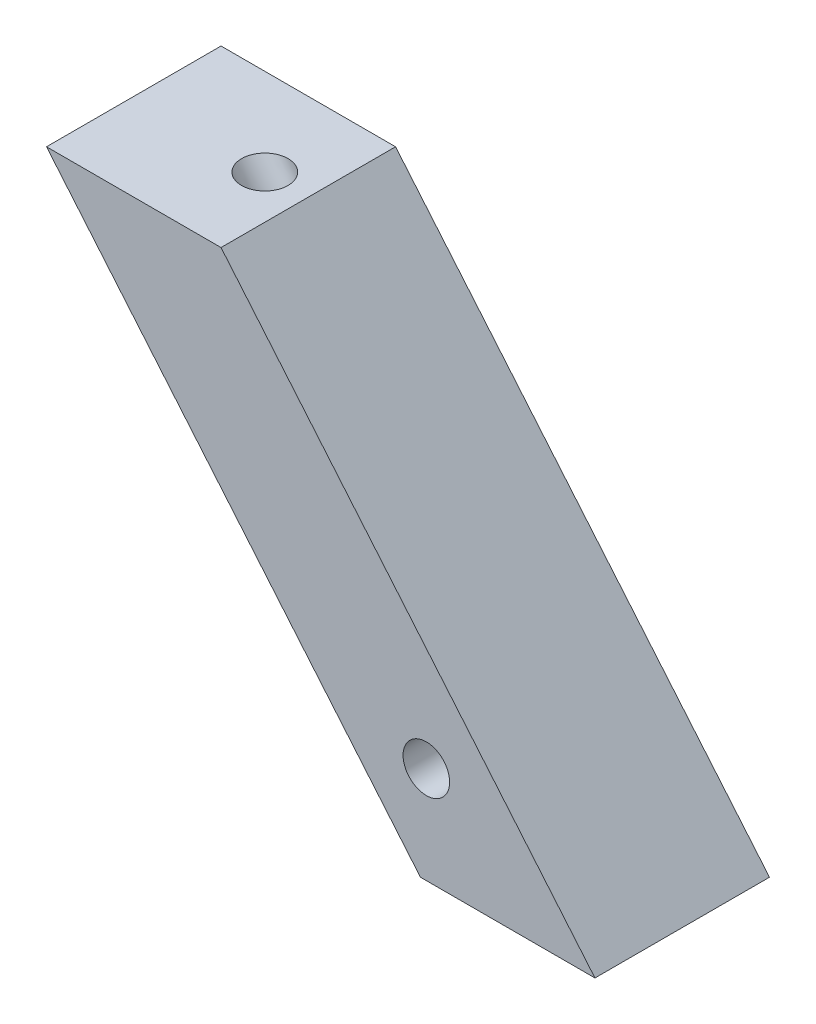
SolidWorks part; units mm, degrees
ref_plane "前视基准面" through (0, 0, 0) normal (0, 0, 1) x (1, 0, 0)
ref_plane "上视基准面" through (0, 0, 0) normal (0, 1, 0) x (1, 0, 0)
ref_plane "右视基准面" through (0, 0, 0) normal (1, 0, 0) x (0, 0, -1)
other "Configuration Table"
sketch "草图1" plane through (0, 0, 0) normal (0, 1, 0) x (1, 0, 0)
  line L1 (-73.0693, 17.1535) -> (16.9307, 17.1535)
  line L2 (-73.0693, 17.1535) -> (-73.0693, -72.8465)
  line L3 (-73.0693, -72.8465) -> (16.9307, -72.8465)
  line L4 (16.9307, 17.1535) -> (16.9307, -72.8465)
  dimension "D1" = 90
sketch "草图2" plane through (0, 0, 0) normal (0, 0, 1) x (1, 0, 0)
  line L0 (-28.0693, 0) -> (-220.9056, 229.8133)
  line L1 (-73.0693, 0) -> (16.9307, 0) construction
  dimension "D1" = 300
  dimension "D2" = 50
sweep "扫描1" add profiles "草图1" path "草图2"
sketch "草图3" plane through (0, 0, 0) normal (0, -1, 0) x (1, 0, 0)
  line L0 (-28.0693, 72.8465) -> (-28.0693, -17.1535) construction
  line L1 (-73.0693, 72.8465) -> (16.9307, 72.8465) construction
  line L2 (16.9307, -17.1535) -> (-73.0693, -17.1535) construction
  line L3 (-73.0693, 27.8465) -> (16.9307, 27.8465) construction
  line L4 (-73.0693, -17.1535) -> (-73.0693, 72.8465) construction
  line L5 (16.9307, 72.8465) -> (16.9307, -17.1535) construction
  point P12 (-5.0693, 50.8465)
  point P14 (-5.0693, 4.8465)
  point P15 (-51.0693, 4.8465)
  point P16 (-51.0693, 50.8465)
  dimension "D1" = 46
  dimension "D2" = 46
hole_wizard "M4 螺纹孔1" positions "3D草图1" profile "草图4" tap size "M4" standard "GB"
sketch3d "3D草图1"
  point P0 (-51.0693, 0, 50.8465)
  point P3 (-5.0693, 0, 50.8465)
  point P6 (-5.0693, 0, 4.8465)
  point P9 (-51.0693, 0, 4.8465)
sketch "草图4" plane through (-51.0693, 0, 50.8465) normal (1, 0, 0) x (0, 0, -1)
  line L0 (0, 0) -> (0, 16.9914)
  line L1 (0, 16.9914) -> (1.65, 16)
  line L2 (1.65, 16) -> (1.65, 0)
  line L5 (1.65, 0) -> (0, 0)
  line L10 (0, 16.9914) -> (-1.65, 16) construction
  line L11 (0, -6.35) -> (0, 107.95) construction
  dimension "螺纹孔钻头直径" = 3.3
  dimension "螺纹孔钻头深度" = 16
  dimension "导头角度" = 118
cosmetic thread "孔螺蚊线1" parameters "D1"=18, "D2"=4
cosmetic thread "孔螺蚊线2" parameters "D1"=18, "D2"=4
cosmetic thread "孔螺蚊线3" parameters "D1"=18, "D2"=4
cosmetic thread "孔螺蚊线4" parameters "D1"=18, "D2"=4
sketch "草图5" plane through (0, 0, 0) normal (0, -1, 0) x (1, 0, 0)
  line L0 (-28.0693, 72.8465) -> (-28.0693, -17.1535) construction
  circle A0 centre (-28.0693, 27.8465) radius 12
  dimension "D1" = 24
sketch "草图8" plane through (0, 0, 72.8465) normal (0, 0, 1) x (1, 0, 0)
  line L0 (-28.0693, 0) -> (-198.316, 229.8133)
  line L3 (-73.0693, 0) -> (16.9307, 0) construction
  line L4 (-265.9056, 229.8133) -> (-175.9056, 229.8133) construction
sweep "切除-扫描2" cut profiles "草图5" path "草图8"
sketch "草图9" plane through (0, 0, -17.1535) normal (0, 0, -1) x (-1, 0, 0)
  line L0 (220.9056, 229.8133) -> (28.0693, 0) construction
  line L1 (175.9056, 229.8133) -> (265.9056, 229.8133) construction
  line L2 (73.0693, 0) -> (-16.9307, 0) construction
  circle A0 centre (70.0243, 50) radius 12
  dimension "D1" = 24
  dimension "D2" = 50
extrude "切除-拉伸1" cut sketch "草图9" against normal up to next contours A0
